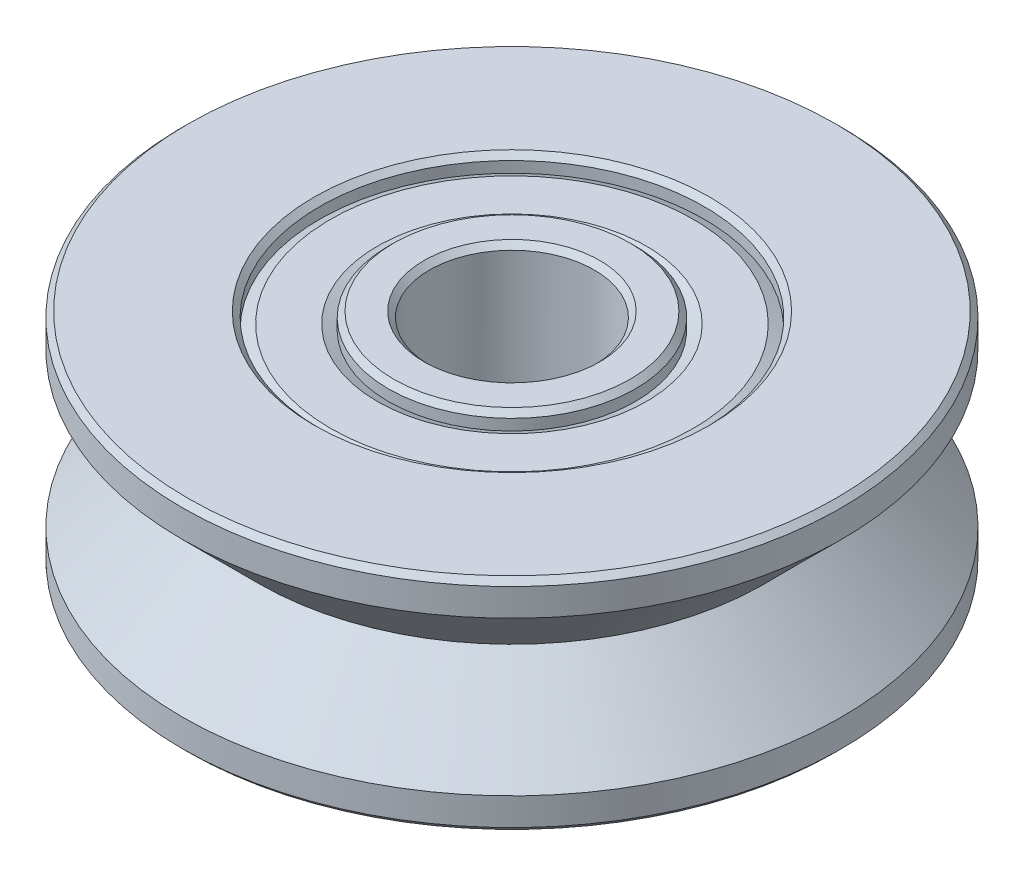
SolidWorks part; units mm, degrees
ref_plane "Front Plane" through (0, 0, 0) normal (0, 0, 1) x (1, 0, 0)
ref_plane "Top Plane" through (0, 0, 0) normal (0, 1, 0) x (1, 0, 0)
ref_plane "Right Plane" through (0, 0, 0) normal (1, 0, 0) x (0, 0, -1)
sketch "Sketch1" plane through (0, 0, 0) normal (1, 0, 0) x (0, 0, -1)
  line L0 (6, 1.4) -> (4.6, 0)
  line L1 (0, 2) -> (6, 2)
  line L2 (0, 2) -> (0, -2) construction
  line L3 (0, -2) -> (6, -2)
  line L4 (6, 2) -> (6, -2)
  line L5 (4.6, 0) -> (6, -1.4)
  line L6 (4.6, 0) -> (0, 0) construction
  line L7 (1.5, 2) -> (1.5, -2)
  dimension "D1" = 4
  dimension "D2" = 6
  dimension "D3" = 1.4
  dimension "D4" = 2.8
  dimension "D5" = 3
revolve "Revolve1" add sketch "Sketch1" angle 360 about L2 region at (0, 0, -3.5321)
sketch "Sketch3" plane through (0, 0, 0) normal (1, 0, 0) x (0, 0, -1)
  line L0 (6, 2) -> (6, -2) construction
  line L1 (1.5, 2) -> (1.5, -2) construction
  line L2 (0, 2) -> (6, 2) construction
  line L3 (6, 2) -> (6, -2) construction
  line L4 (1.5, 2) -> (1.5, -2)
  line L5 (0, 2) -> (6, 2) construction
  line L6 (2.25, 2) -> (3.5, 2)
  line L7 (2.25, 2) -> (2.25, 1.7)
  line L8 (2.25, 1.7) -> (2.45, 1.8)
  line L9 (2.45, 1.8) -> (3.3, 1.8)
  line L10 (3.3, 1.8) -> (3.5, 1.7)
  line L11 (3.5, 1.7) -> (3.5, 2)
  line L12 (4.6, 0) -> (6, -1.4) construction
  line L13 (6, 1.4) -> (4.6, 0) construction
  line L14 (0, 2) -> (0, -2) construction
  line L15 (4.6, 0) -> (6, -1.4)
  line L16 (6, 1.4) -> (4.6, 0) construction
  line L17 (0, 2) -> (0, -2) construction
  line L18 (2.25, 1.7) -> (3.5, 1.7) construction
  line L19 (2.875, 1.7) -> (2.875, 2) construction
  dimension "D1" = 2.5
  dimension "D2" = 0.2
  dimension "D3" = 0.75
  dimension "D4" = 0.1
  dimension "D5" = 0.2
revolve "Cut-Revolve2" cut sketch "Sketch3" angle 360 about L17 region at (0, 1.8901, -2.875)
mirror "Mirror1" about plane through (0, 0, 0) normal (0, 1, 0) of "Cut-Revolve2"
chamfer "Chamfer1" distance 0.1 angle 45 8 edges at (0, -2, 3.5) (0, 2, 3.5) (0, -2, 6) (0, 2, 6) (0, -2, 2.25) (0, 2, 2.25) (0, 2, 1.5) (0, -2, 1.5)
